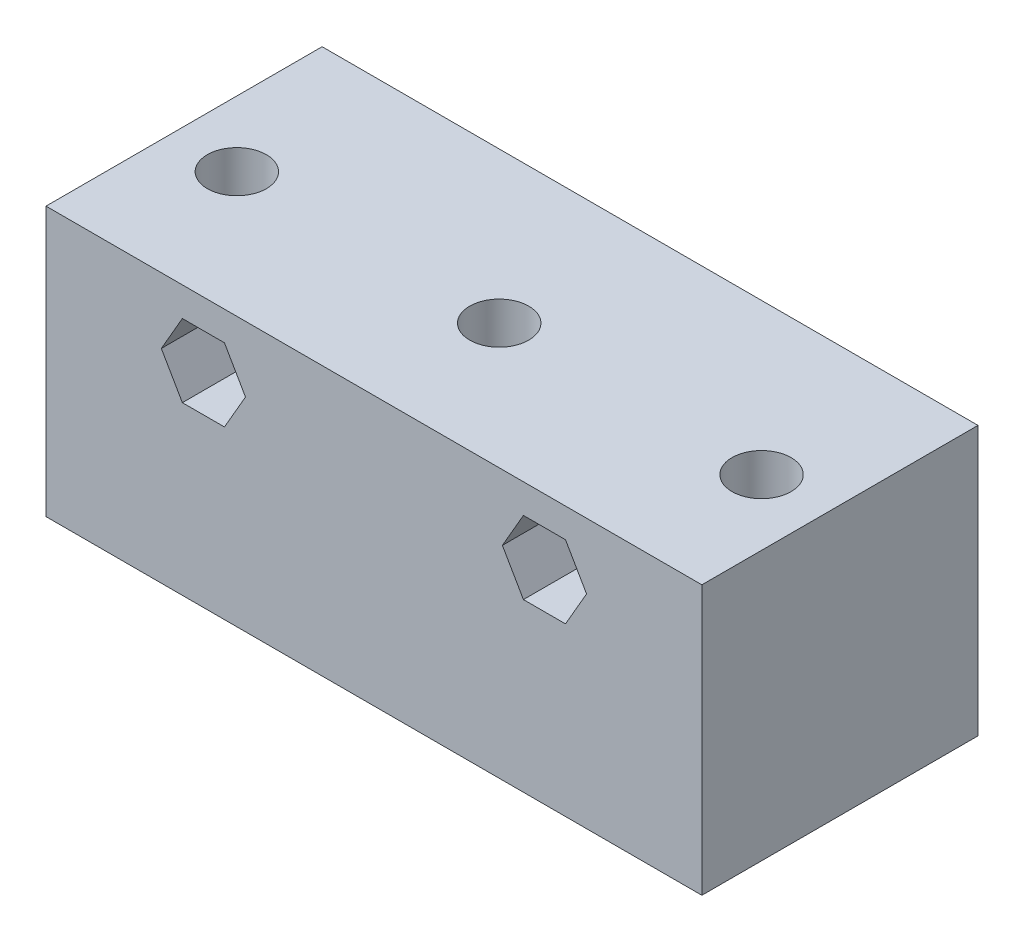
SolidWorks part; units mm, degrees
ref_plane "Front Plane" through (0, 0, 0) normal (0, 0, 1) x (1, 0, 0)
ref_plane "Top Plane" through (0, 0, 0) normal (0, 1, 0) x (1, 0, 0)
ref_plane "Right Plane" through (0, 0, 0) normal (1, 0, 0) x (0, 0, -1)
sketch "Sketch1" plane through (0, 0, 0) normal (0, 0, 1) x (1, 0, 0)
  line L0 (20.7921, -4.4437) -> (27.2079, -4.4437)
  line L1 (0, 0) -> (100, 0)
  line L2 (0, 0) -> (0, -41)
  line L3 (0, -41) -> (100, -41)
  line L4 (100, 0) -> (100, -41)
  line L5 (27.2079, -4.4437) -> (30.4158, -10)
  line L6 (30.4158, -10) -> (27.2079, -15.5563)
  line L7 (27.2079, -15.5563) -> (20.7921, -15.5563)
  line L8 (20.7921, -15.5563) -> (17.5842, -10)
  line L9 (17.5842, -10) -> (20.7921, -4.4437)
  line L10 (24, -4.4437) -> (24, -15.5563) construction
  line L11 (17.5842, -10) -> (30.4158, -10)
  line L12 (50, 0) -> (50, -41) construction
  line L13 (82.4158, -10) -> (79.2079, -4.4437)
  line L14 (0, 0) -> (0, -41)
  line L15 (79.2079, -15.5563) -> (82.4158, -10)
  line L16 (72.7921, -15.5563) -> (79.2079, -15.5563)
  line L17 (69.5842, -10) -> (72.7921, -15.5563)
  line L18 (72.7921, -4.4437) -> (69.5842, -10)
  line L19 (79.2079, -4.4437) -> (72.7921, -4.4437)
  circle A0 centre (24, -10) radius 4.5
  circle A1 centre (76, -10) radius 4.5
  point P15 (24, -10)
  point P17 (24, -10)
  point P27 (0, 0)
  dimension "D5" = 9
  dimension "D1" = 100
  dimension "D2" = 41
  dimension "D3" = 24
  dimension "D4" = 52
  dimension "D6" = 10
  dimension "D7" = 11.1125
  dimension "D8" = 60
extrude "Boss-Extrude1" add sketch "Sketch1" along normal blind 42.1 contours L4 L1 L2 L3 L19 L13 L15 L16 L17 L18 L8 L9 L0 L5 L6 L7 region at (50, -21.0779, 0)
ref_plane "Plane1" through (0, 0, 0) normal (0, -1, 0) x (-1, 0, 0)
sketch "Sketch2" plane through (0, 0, 0) normal (0, -1, 0) x (-1, 0, 0)
  line L3 (-100, -42.1) -> (-100, 0) construction
  line L4 (0, -42.1) -> (0, 0) construction
  line L5 (0, 0) -> (-100, 0) construction
  circle A0 centre (-10, -23) radius 4.5
  circle A1 centre (-50, -23) radius 4.5
  circle A2 centre (-90, -23) radius 4.5
  point P6 (0, 0)
  point P9 (0, 0)
  point P10 (-82.4509, -23)
  point P11 (-44.1271, -23)
  point P12 (-5.6068, -23)
  point P13 (-90.4558, -23)
  point P14 (0, 0)
  dimension "D2" = 9
  dimension "D1" = 23
  dimension "D3" = 50
  dimension "D4" = 10
  dimension "D5" = 10
extrude "Cut-Extrude1" cut sketch "Sketch2" along normal up to surface (41 mm away) up to face at (50, -41, 21.05)
extrude "Boss-Extrude2" add sketch "Sketch1<3>" along normal blind 10 contours A0 L11 L5 L0 L9 | A0 L11 L8 L7 L6 | L13 L19 L18 L17 L16 L15 A1 region at (24, -4.5836, 0) region at (18.5421, -10.1398, 0) region at (80.6648, -12.6933, 0)
sketch "Sketch1<3>" plane through (0, 0, 0) normal (0, 0, 1) x (1, 0, 0) same geometry as "Sketch1"
equation "\"D3@Sketch1\"=(\"D1@Sketch1\"-\"D4@Sketch1\")/2"
